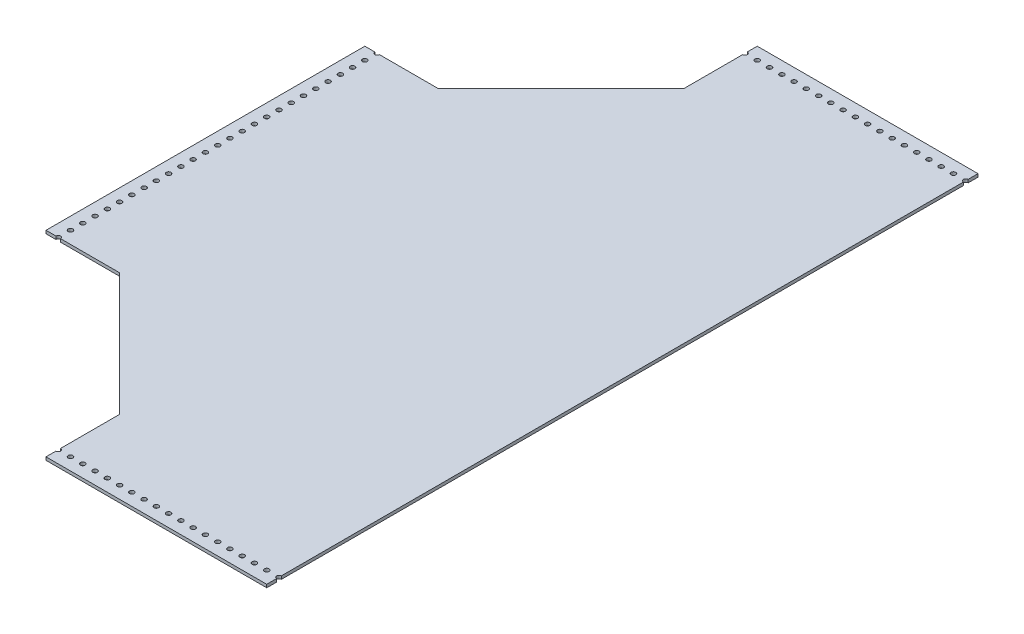
SolidWorks part; units mm, degrees
material "ABS PC"
ref_plane "Front Plane" through (0, 0, 0) normal (0, 0, 1) x (1, 0, 0)
ref_plane "Top Plane" through (0, 0, 0) normal (0, 1, 0) x (1, 0, 0)
ref_plane "Right Plane" through (0, 0, 0) normal (1, 0, 0) x (0, 0, -1)
sketch "Sketch1" plane through (0, 0, 0) normal (0, 1, 0) x (1, 0, 0)
  line L1 (-317.5, -368.3) -> (317.5, -368.3)
  line L2 (-317.5, -368.3) -> (-317.5, 368.3)
  line L3 (-317.5, 368.3) -> (317.5, 368.3)
  line L4 (317.5, -368.3) -> (317.5, 368.3)
  line L5 (-317.5, -368.3) -> (317.5, 368.3) construction
  line L6 (-317.5, 368.3) -> (317.5, -368.3) construction
  point P0 (0, 0)
  dimension "D1" = 635
  dimension "D2" = 736.6
extrude "Base" add sketch "Sketch1" along normal blind 3.175
sketch "Sketch3" plane through (0, 3.175, 0) normal (0, 1, 0) x (1, 0, 0)
  line L0 (317.5, -368.3) -> (317.5, 368.3) construction
  line L6 (317.5, 368.3) -> (-317.5, 368.3) construction
  line L7 (-317.5, 368.3) -> (-317.5, -368.3) construction
  circle A0 centre (-304.8, 355.6) radius 2.413
  circle A1 centre (304.8, 355.6) radius 2.413
  dimension "D1" = 4.826
  dimension "D2" = 4.826
  dimension "D3" = 12.7
  dimension "D4" = 12.7
  dimension "D5" = 12.7
  dimension "D6" = 12.7
extrude "Initial Pattern Hole" cut sketch "Sketch3" against normal through all
pattern_linear "Hole Pattern 1" count 58 spacing 12.7 along (0, 0, 1) of "Initial Pattern Hole"
pattern_linear "Hole Pattern 2" count 48 spacing 12.7 along (1, 0, 0) of face at (-304.8, 0, 358.013) of face at (-304.8, 0, -353.187)
sketch "Sketch2" plane through (0, 0, 0) normal (0, -1, 0) x (-1, 0, 0)
  line L16 (-317.5, 368.3) -> (-317.5, 184.15)
  line L17 (-317.5, -368.3) -> (-317.5, 368.3) construction
  line L18 (-317.5, 184.15) -> (-292.1004, 184.15)
  line L19 (-292.1004, 184.15) -> (-133.35, 342.9004)
  line L20 (-133.35, 342.9004) -> (-133.35, 368.3)
  line L21 (-317.5, 368.3) -> (317.5, 368.3) construction
  line L22 (-133.35, 368.3) -> (-317.5, 368.3)
  line L23 (133.35, 368.3) -> (317.5, 368.3)
  line L24 (317.5, 368.3) -> (317.5, 184.15)
  line L25 (317.5, 368.3) -> (317.5, -368.3) construction
  line L26 (317.5, 184.15) -> (292.1004, 184.15)
  line L27 (292.1004, 184.15) -> (133.35, 342.9004)
  line L28 (133.35, 342.9004) -> (133.35, 368.3)
  line L29 (317.5, -368.3) -> (317.5, -184.15)
  line L30 (317.5, -184.15) -> (292.1004, -184.15)
  line L31 (292.1004, -184.15) -> (133.35, -342.9004)
  line L32 (133.35, -342.9004) -> (133.35, -368.3)
  line L33 (317.5, -368.3) -> (307.213, -368.3) construction
  line L34 (133.35, -368.3) -> (317.5, -368.3)
  line L35 (-133.35, -368.3) -> (-133.35, -342.9004)
  line L36 (-133.35, -342.9004) -> (-292.1004, -184.15)
  line L37 (-292.1004, -184.15) -> (-317.5, -184.15)
  line L38 (-317.5, -184.15) -> (-317.5, -368.3)
  line L39 (-317.5, -368.3) -> (-133.35, -368.3)
  dimension "D1" = 184.15
extrude "Module Cutout" [suppressed] cut sketch "Sketch2" against normal through all
sketch "Sketch4" plane through (0, 3.175, 0) normal (0, 1, 0) x (1, 0, 0)
  line L24 (-317.5, 165.1) -> (-241.3, 165.1)
  line L25 (-317.5, 368.3) -> (-317.5, -368.3) construction
  line L26 (-241.3, 165.1) -> (-114.3, 292.1)
  line L27 (-114.3, 292.1) -> (-114.3, 368.3)
  line L28 (317.5, 368.3) -> (-317.5, 368.3) construction
  line L29 (-317.5, -368.3) -> (-114.3, -368.3)
  line L30 (-114.3, -368.3) -> (-114.3, -292.1)
  line L31 (-114.3, -292.1) -> (-241.3, -165.1)
  line L32 (-241.3, -165.1) -> (-317.5, -165.1)
  line L33 (-317.5, -165.1) -> (-317.5, -368.3)
  line L34 (-317.5, 165.1) -> (-317.5, 368.3)
  line L35 (-317.5, 368.3) -> (-114.3, 368.3)
  line L36 (317.5, 368.3) -> (114.3, 368.3)
  line L37 (114.3, 368.3) -> (114.3, -368.3)
  line L39 (317.5, 152.4) -> (317.5, 361.95) construction
  line L40 (317.5, -368.3) -> (317.5, 368.3)
  line L44 (-302.387, -368.3) -> (302.387, -368.3) construction
  line L45 (114.3, -368.3) -> (317.5, -368.3)
  dimension "D1" = 76.2
  dimension "D2" = 76.2
  dimension "D3" = 203.2
  dimension "D4" = 203.2
  dimension "D6" = 203.2
extrude "Top Module Cutout" cut sketch "Sketch4" against normal through all
